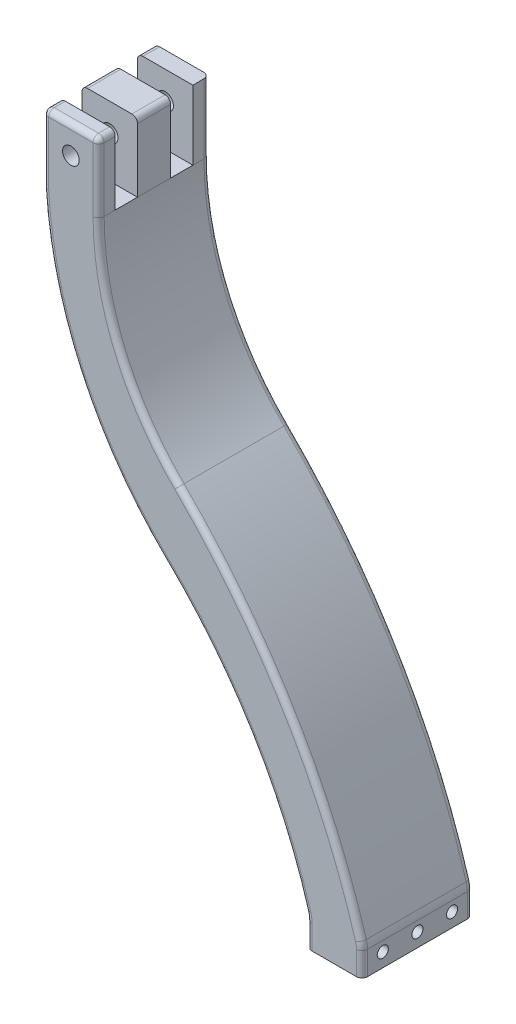
SolidWorks part; units mm, degrees
ref_plane "Front Plane" through (0, 0, 0) normal (0, 0, 1) x (1, 0, 0)
ref_plane "Top Plane" through (0, 0, 0) normal (0, 1, 0) x (1, 0, 0)
ref_plane "Right Plane" through (0, 0, 0) normal (1, 0, 0) x (0, 0, -1)
sketch "Sketch1" plane through (0, 0, 0) normal (0, 0, 1) x (1, 0, 0)
  line L0 (-82.2697, 98.3583) -> (-62.2697, 98.3583)
  line L3 (12.7303, -83.0658) -> (12.7303, -91.6417)
  line L4 (12.7303, -91.6417) -> (32.7303, -91.6417)
  line L5 (32.7303, -91.6417) -> (32.7303, -83.0909)
  line L6 (0, 0) -> (328.3387, 0) construction
  arc A3 (-38.4836, 3.6003) -> (-82.2697, 98.3583) centre (61.7733, 107.4227) cw
  arc A4 (-62.2697, 98.3583) -> (-33.4397, 29.2804) centre (34.9019, 98.3583) ccw
  arc A5 (-38.4836, 3.6003) -> (12.3219, -80.2372) centre (-171.9049, -134.5659) cw
  arc A6 (-33.4397, 29.2804) -> (32.3107, -80.2245) centre (-214.9763, -154.212) cw
  arc A7 (12.7303, -83.0658) -> (12.3219, -80.2372) centre (2.7303, -83.0658) ccw
  arc A8 (32.7303, -83.0909) -> (32.3107, -80.2245) centre (22.7303, -83.0909) ccw
  point P30 (12.7303, -81.6417)
  point P33 (32.7303, -81.6417)
  dimension "D4" = 10
  dimension "D6" = 10
  dimension "D7" = 10
  dimension "D1" = 115
  dimension "D2" = 20
  dimension "D3" = 20
  dimension "D5" = 190
extrude "Boss-Extrude1" add sketch "Sketch1" along normal mid plane 40
sketch "Sketch6" plane through (0, 98.3583, 0) normal (0, 1, 0) x (1, 0, 0)
  line L4 (-62.2697, 20) -> (-82.2697, 20)
  line L5 (-82.2697, 20) -> (-82.2697, -20)
  line L6 (-82.2697, -20) -> (-62.2697, -20)
  line L7 (-62.2697, -20) -> (-62.2697, 20)
  line L8 (-62.2697, 20) -> (-82.2697, 20)
  line L9 (-82.2697, 20) -> (-82.2697, -20)
  line L10 (-82.2697, -20) -> (-62.2697, -20)
  line L11 (-62.2697, -20) -> (-62.2697, 20)
  dimension "D1" = 0
extrude "Boss-Extrude2" add sketch "Sketch6" along normal blind 25
sketch "Sketch8" plane through (0, 123.3583, 0) normal (0, 1, 0) x (1, 0, 0)
  line L0 (0, 0) -> (-37.6085, 0) construction
  line L1 (-72.2697, 0) -> (-72.2697, -20) construction
  line L2 (-62.2697, -20) -> (-62.2697, 20) construction
  line L3 (-82.2697, -6) -> (-62.2697, -6)
  line L4 (-82.2697, -6) -> (-82.2697, -14)
  line L5 (-82.2697, -14) -> (-62.2697, -14)
  line L6 (-62.2697, -6) -> (-62.2697, -14)
  line L7 (-82.2697, -6) -> (-62.2697, -14) construction
  line L8 (-82.2697, -14) -> (-62.2697, -6) construction
  line L9 (-82.2697, 14) -> (-62.2697, 6) construction
  line L10 (-82.2697, 6) -> (-62.2697, 14) construction
  line L11 (-62.2697, 6) -> (-62.2697, 14)
  line L12 (-82.2697, 14) -> (-62.2697, 14)
  line L13 (-82.2697, 6) -> (-82.2697, 14)
  line L14 (-82.2697, 6) -> (-62.2697, 6)
  point P5 (-72.2697, -10)
  point P16 (-72.2697, 10)
  dimension "D1" = 20
  dimension "D2" = 8
  dimension "D3" = 10
extrude "Cut-Extrude7" cut sketch "Sketch8" against normal blind 25 and the other way through all
sketch "Sketch9" plane through (0, 0, 20) normal (0, 0, 1) x (1, 0, 0)
  line L0 (-82.2697, 123.3583) -> (-62.2697, 123.3583) construction
  line L1 (-82.2697, 123.3583) -> (-82.2697, 98.3583) construction
  circle A0 centre (-72.2697, 113.3583) radius 3
  dimension "D1" = 6
  dimension "D2" = 10
  dimension "D3" = 10
extrude "Cut-Extrude8" cut sketch "Sketch9" against normal through all
fillet "Fillet1" radius 2 14 edges at (-62.2697, 110.8583, -20) (-54.773, 60.932, -20) (-54.773, 60.932, 20) (-62.2697, 110.8583, 20) (-7.6421, -35.0226, 20) (6.3159, -21.3408, -20) (6.3159, -21.3408, 20) (-69.2434, 46.8821, 20) (12.7303, -87.3538, 20) (12.6277, -81.6369, 20) (32.7303, -87.3663, -20) (32.7303, -87.3663, 20) (32.6248, -81.6424, -20) (32.6248, -81.6424, 20)
fillet "Fillet2" radius 2 8 edges at (-82.2697, 123.3583, -17) (-82.2697, 123.3583, 0) (-62.2697, 123.3583, 0) (-82.2697, 123.3583, 16) (-62.2697, 123.3583, 16) (-62.8555, 123.3583, 19.4142) (-72.2697, 123.3583, 20) (-81.6839, 123.3583, 19.4142)
sketch "Sketch10" plane through (0, -91.6417, 0) normal (0, -1, 0) x (1, 0, 0)
  line L8 (28.7303, 16) -> (16.7303, 16)
  line L9 (16.7303, 16) -> (16.7303, -16)
  line L10 (16.7303, -16) -> (28.7303, -16)
  line L11 (28.7303, -16) -> (28.7303, 16)
  line L12 (28.7303, 16) -> (16.7303, 16)
  line L13 (16.7303, 16) -> (16.7303, -16)
  line L14 (16.7303, -16) -> (28.7303, -16)
  line L15 (28.7303, -16) -> (28.7303, 16)
  dimension "D1" = 4
extrude "Cut-Extrude9" cut sketch "Sketch10" against normal blind 10
sketch "Sketch11" plane through (32.7303, 0, 0) normal (1, 0, 0) x (0, 0, -1)
  line L0 (0, -86.6417) -> (0, -107.3364) construction
  line L1 (-18, -91.6417) -> (18, -91.6417) construction
  circle A0 centre (0, -86.6417) radius 2
  circle A1 centre (-12.5, -86.6417) radius 2
  circle A2 centre (12.5, -86.6417) radius 2
  dimension "D1" = 4
  dimension "D2" = 4
  dimension "D3" = 4
  dimension "D4" = 12.5
  dimension "D5" = 12.5
  dimension "D6" = 5
extrude "Cut-Extrude10" cut sketch "Sketch11" against normal through all
